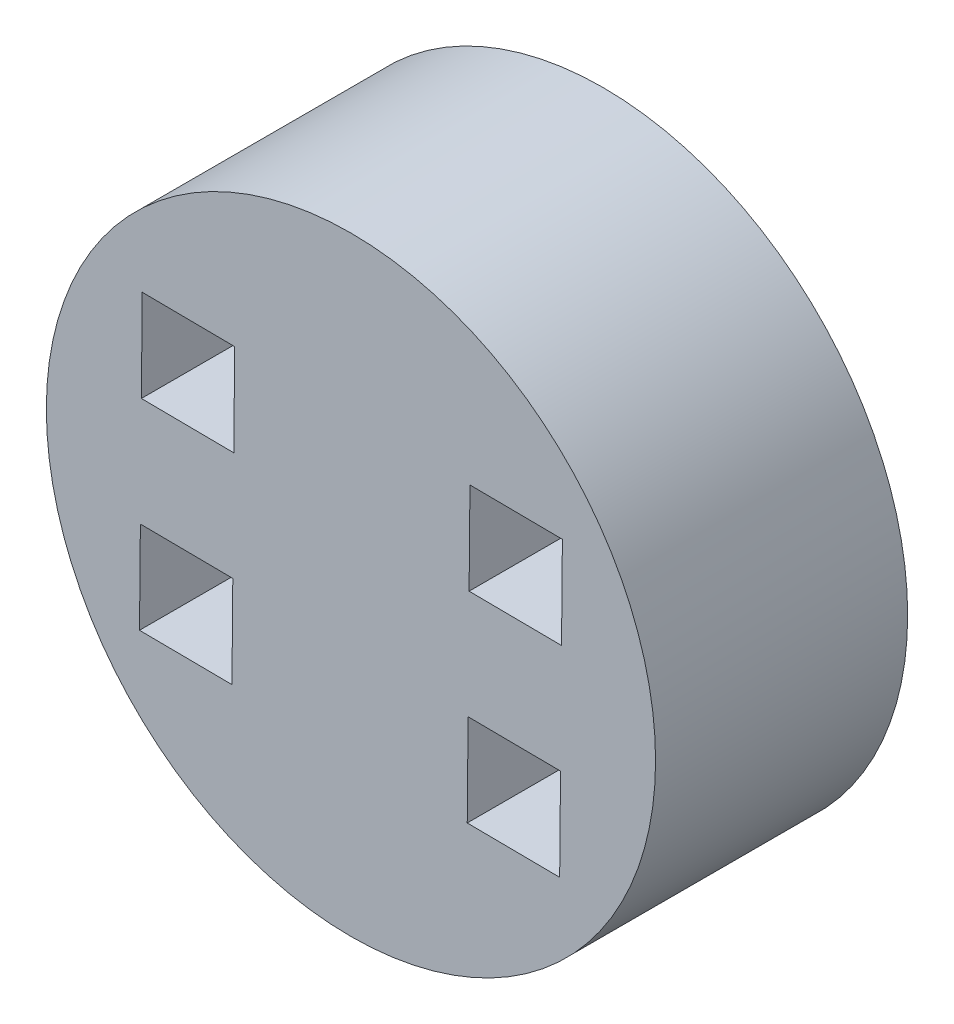
SolidWorks part; units mm, degrees
material "Polyurethane Foam Flexible"
ref_plane "Front Plane" through (0, 0, 0) normal (0, 0, 1) x (1, 0, 0)
ref_plane "Top Plane" through (0, 0, 0) normal (0, 1, 0) x (1, 0, 0)
ref_plane "Right Plane" through (0, 0, 0) normal (1, 0, 0) x (0, 0, -1)
sketch "Sketch1" plane through (0, 0, 0) normal (0, 0, 1) x (1, 0, 0)
  circle A0 centre (0, 0) radius 92.075
  dimension "D1" = 184.15
extrude "Boss-Extrude1" add sketch "Sketch1" along normal blind 76.2
sketch "Sketch7" plane through (0, 0, 0) normal (0, 0, -1) x (-1, 0, 0)
  line L8 (35.1482, 44.7763) -> (35.4061, 16.8375)
  line L9 (63.087, 45.0342) -> (63.3449, 17.0954)
  line L10 (63.087, 45.0342) -> (35.1482, 44.7763)
  line L11 (63.3449, 17.0954) -> (35.4061, 16.8375)
  line L12 (63.6497, -15.9232) -> (35.7109, -16.1811)
  line L13 (63.9075, -43.862) -> (63.6497, -15.9232)
  line L14 (35.9687, -44.1199) -> (35.7109, -16.1811)
  line L15 (63.9075, -43.862) -> (35.9687, -44.1199)
  line L16 (0, 0) -> (-0.563, 61.0017) construction
  line L17 (-35.1482, -44.7763) -> (-35.4061, -16.8375)
  line L18 (-63.087, -45.0342) -> (-35.1482, -44.7763)
  line L19 (-63.087, -45.0342) -> (-63.3449, -17.0954)
  line L20 (-63.3449, -17.0954) -> (-35.4061, -16.8375)
  line L21 (-63.6497, 15.9232) -> (-35.7109, 16.1811)
  line L22 (-63.9075, 43.862) -> (-63.6497, 15.9232)
  line L23 (-63.9075, 43.862) -> (-35.9687, 44.1199)
  line L24 (-35.9687, 44.1199) -> (-35.7109, 16.1811)
extrude "Cut-Extrude3" cut sketch "Sketch7" against normal up to surface (76.2 mm away) up to face at (92.075, 0, 76.2)
